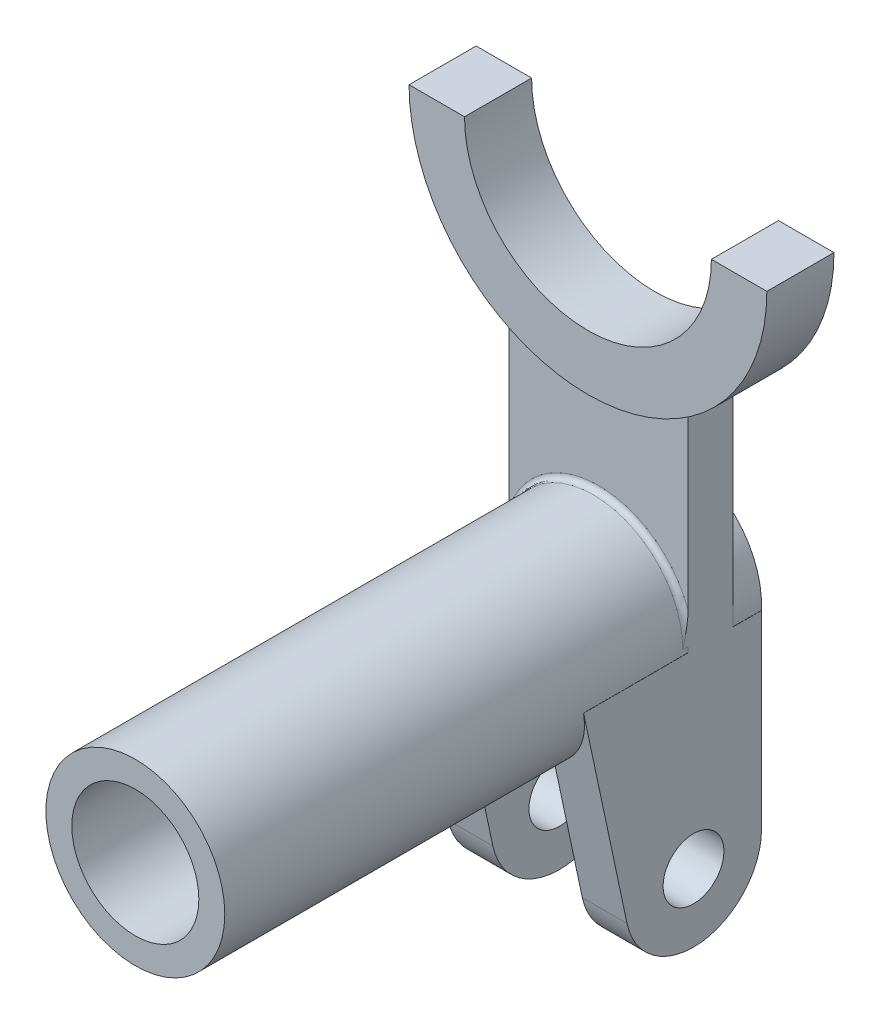
SolidWorks part; units mm, degrees
ref_plane "Alzado" through (0, 0, 0) normal (0, 0, 1) x (1, 0, 0)
ref_plane "Planta" through (0, 0, 0) normal (0, 1, 0) x (1, 0, 0)
ref_plane "Vista lateral" through (0, 0, 0) normal (1, 0, 0) x (0, 0, -1)
sketch "Croquis2" plane through (0, 0, 0) normal (0, 0, 1) x (1, 0, 0)
  line L2 (-25.4, -77.724) -> (25.4, -77.724)
  line L3 (-25.4, -77.724) -> (-25.4, 77.724)
  line L4 (-25.4, 77.724) -> (25.4, 77.724)
  line L5 (25.4, -77.724) -> (25.4, 77.724)
  point P0 (0, 0)
  dimension "D1" = 155.448
  dimension "D2" = 50.8
extrude "Saliente-Extruir1" add sketch "Croquis2" along normal blind 12.7
sketch "Croquis3" plane through (0, 0, 12.7) normal (0, 0, 1) x (1, 0, 0)
  line L0 (0, 130.6877) -> (0, -150.113) construction
  line L1 (25.4, 77.724) -> (-25.4, 77.724) construction
  circle A0 centre (0, -23.876) radius 25.4
  circle A1 centre (0, -23.876) radius 18.034
  dimension "D1" = 50.8
  dimension "D2" = 36.068
  dimension "D3" = 101.6
extrude "Saliente-Extruir2" add sketch "Croquis3" along normal blind 131.572
sketch "Croquis4" plane through (0, 0, 12.7) normal (0, 0, 1) x (1, 0, 0)
  circle A0 centre (0, -23.876) radius 18.034
  circle A1 centre (0, -23.876) radius 18.034 construction
extrude "Cortar-Extruir1" cut sketch "Croquis4" against normal blind 131.572
sketch "Croquis5" plane through (0, 0, 12.7) normal (0, 0, 1) x (1, 0, 0)
  line L0 (0, -23.876) -> (0, 137.8424) construction
  line L1 (25.4, 77.724) -> (-25.4, 77.724) construction
  line L2 (50.8, 77.724) -> (-50.8, 77.724)
  arc A0 (-35.052, 77.724) -> (35.052, 77.724) centre (0, 77.724) ccw
  arc A1 (-50.8, 77.724) -> (50.8, 77.724) centre (0, 77.724) ccw
  line M2 (25.4, -23.876) -> (25.4, 77.724)
  line M4 (-25.4, 77.724) -> (-25.4, -23.876)
  dimension "D1" = 70.104
  dimension "D2" = 101.6
extrude "Saliente-Extruir3" add sketch "Croquis5" along normal blind 3.048 and the other way blind 16.002 contours A1 L2 A0 M2 | L0 A1 A0 M2 | A1 L0 A0 M4 | L2 A1 A0 M4
sketch "Croquis6" plane through (0, 0, 12.7) normal (0, 0, 1) x (1, 0, 0)
  circle A0 centre (125.6562, 86.955) radius 0.3526
sketch "Croquis7" plane through (0, 0, 15.748) normal (0, 0, 1) x (1, 0, 0)
  line L0 (25.4, 77.724) -> (-25.4, 77.724) construction
  circle A0 centre (0, 77.724) radius 35.052
  arc A1 (-35.052, 77.724) -> (35.052, 77.724) centre (0, 77.724) ccw construction
extrude "Cortar-Extruir2" cut sketch "Croquis7" against normal through all
sketch "Croquis8" plane through (0, 0, 12.7) normal (0, 0, 1) x (1, 0, 0)
  line L4 (0, 18.9493) -> (0, -99.8835) construction
  circle A0 centre (0, -23.876) radius 25.4 construction
  arc A1 (-25.4, -23.876) -> (-12.7, -45.873) centre (0, -23.876) ccw
  arc A2 (-25.4, -23.876) -> (25.4, -23.876) centre (0, -23.876) ccw construction
  circle A3 centre (0, -23.876) radius 25.4
extrude "Saliente-Extruir5" add sketch "Croquis8" against normal blind 20.828 contours A3
sketch "Croquis11" plane through (0, 0, -8.128) normal (0, 0, -1) x (-1, 0, 0)
  circle A0 centre (0, -23.876) radius 18.034
  circle A2 centre (0, -23.876) radius 25.4 construction
  dimension "D1" = 36.068
extrude "Cortar-Extruir3" cut sketch "Croquis11" against normal blind 20.828
sketch "Croquis12" plane through (-25.4, 0, 0) normal (-1, 0, 0) x (0, 0, 1)
  line L0 (-8.128, -79.248) -> (-8.128, -25.4)
  line L1 (-8.128, 1.524) -> (-8.128, -49.276) construction
  line L2 (42.377, -25.4) -> (30.0568, -83.2678)
  line L3 (-8.128, -25.4) -> (42.377, -25.4)
  arc A0 (-8.128, -79.248) -> (30.0568, -83.2678) centre (11.176, -79.248) ccw
  dimension "D1" = 38.608
  dimension "D2" = 79.248
  dimension "D3" = 53.848
  dimension "D4" = 50.505
extrude "Saliente-Extruir6" add sketch "Croquis12" against normal blind 12.7
sketch "Croquis14" plane through (25.4, 0, 0) normal (1, 0, 0) x (0, 0, -1)
  line L0 (-30.0568, -83.2678) -> (-42.377, -25.4)
  line L1 (-42.377, -25.4) -> (8.128, -25.4)
  line L2 (8.128, -25.4) -> (8.128, -79.248)
  arc A0 (-30.0568, -83.2678) -> (8.128, -79.248) centre (-11.176, -79.248) ccw
  arc A1 (-30.0568, -83.2678) -> (8.128, -79.248) centre (-11.176, -79.248) ccw construction
extrude "Saliente-Extruir7" add sketch "Croquis14" against normal blind 12.7
sketch "Croquis16" plane through (0, 0, -8.128) normal (0, 0, -1) x (-1, 0, 0)
  circle A0 centre (0, -23.876) radius 18.034
  arc A1 (17.9695, -25.4) -> (-17.9695, -25.4) centre (0, -23.876) ccw construction
extrude "Cortar-Extruir4" cut sketch "Croquis16" against normal through all
sketch "Croquis18" plane through (0, 0, 12.7) normal (0, 0, 1) x (1, 0, 0)
  line L0 (-12.7, -77.724) -> (12.7, -77.724)
  line L1 (12.7, -77.724) -> (12.7, -45.873)
  line L2 (-12.7, -77.724) -> (-12.7, -45.873)
  arc A0 (-12.7, -45.873) -> (12.7, -45.873) centre (0, -23.876) ccw
  circle A1 centre (0, -23.876) radius 25.4 construction
extrude "Cortar-Extruir5" cut sketch "Croquis18" against normal through all
sketch "Croquis19" plane through (-25.4, 0, 0) normal (-1, 0, 0) x (0, 0, 1)
  circle A0 centre (11.176, -79.248) radius 8.636
  dimension "D1" = 17.272
extrude "Cortar-Extruir6" cut sketch "Croquis19" against normal through all
ref_plane "Plano1" through (-25.4, -79.248, -8.128) normal (0, -1, 0) x (-1, 0, 0)
fillet "Redondeo2" radius 1.524 1 edges at (0, 1.524, 12.7) type face fillet first side face at (0, 9.5755, 12.7) second side face at (25.4, -23.876, 144.272)
